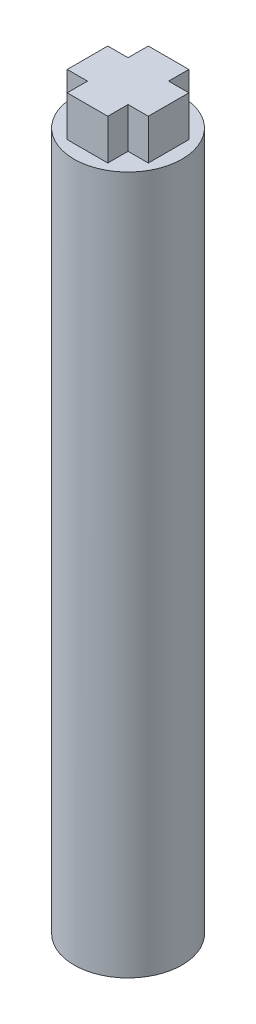
SolidWorks part; units mm, degrees
ref_plane "前视基准面" through (0, 0, 0) normal (0, 0, 1) x (1, 0, 0)
ref_plane "上视基准面" through (0, 0, 0) normal (0, 1, 0) x (1, 0, 0)
ref_plane "右视基准面" through (0, 0, 0) normal (1, 0, 0) x (0, 0, -1)
sketch "草图1" plane through (0, 0, 0) normal (0, 1, 0) x (1, 0, 0)
  line L1 (2.6744, -1.6246) -> (2.7442, 1.5038)
  line L2 (2.7442, 1.5038) -> (0.0698, 3.1285)
  line L3 (0.0698, 3.1285) -> (-2.6744, 1.6246)
  line L4 (-2.6744, 1.6246) -> (-2.7442, -1.5038)
  line L5 (-2.7442, -1.5038) -> (-0.0698, -3.1285)
  line L6 (-0.0698, -3.1285) -> (2.6744, -1.6246)
  circle A0 centre (0, 0) radius 4
  circle A1 centre (0, 0) radius 2.71 construction
  dimension "D1" = 8
  dimension "D2" = 2.71
extrude "凸台-拉伸1" add sketch "草图1" along normal blind 4.65
sketch "草图2" plane through (0, 4.65, 0) normal (0, 1, 0) x (1, 0, 0)
  circle A0 centre (0, 0) radius 4
extrude "凸台-拉伸2" add sketch "草图2" along normal blind 45
sketch "草图3" plane through (0, 4.65, 0) normal (0, -1, 0) x (1, 0, 0)
  circle A0 centre (0, 0) radius 2
  dimension "D1" = 4
extrude "切除-拉伸1" cut sketch "草图3" against normal blind 45
sketch "草图4" plane through (0, 49.65, 0) normal (0, 1, 0) x (1, 0, 0)
  circle A0 centre (0, 0) radius 4
extrude "凸台-拉伸3" add sketch "草图4" along normal blind 2
sketch "草图5" plane through (0, 51.65, 0) normal (0, 1, 0) x (1, 0, 0)
  line L0 (-1.5, 3) -> (-1.5, -3)
  line L1 (-1.5, 3) -> (1.5, 3)
  line L2 (-1.5, -3) -> (1.5, -3)
  line L3 (1.5, 3) -> (1.5, -3)
  circle A0 centre (0, 0) radius 4 construction
  dimension "D1" = 6
  dimension "D2" = 3
  dimension "D3" = 3
  dimension "D4" = 1.5
extrude "凸台-拉伸4" add sketch "草图5" along normal blind 3
sketch "草图6" plane through (0, 51.65, 0) normal (0, 1, 0) x (1, 0, 0)
  line L0 (-3, -1.5) -> (3, -1.5)
  line L1 (-3, -1.5) -> (-3, 1.5)
  line L2 (3, -1.5) -> (3, 1.5)
  line L3 (-3, 1.5) -> (3, 1.5)
  line L4 (-1.5, 3) -> (-1.5, -3) construction
  line L5 (1.5, -3) -> (1.5, 3) construction
  line L6 (1.5, 3) -> (-1.5, 3) construction
  line L7 (-1.5, -3) -> (1.5, -3) construction
  dimension "D1" = 1.5
  dimension "D2" = 1.5
  dimension "D3" = 1.5
  dimension "D4" = 1.5
extrude "凸台-拉伸5" add sketch "草图6" along normal blind 3
sketch "草图7" plane through (0, 0, 0) normal (0, -1, 0) x (1, 0, 0)
  circle A0 centre (0, 0) radius 6.0234
extrude "凸台-拉伸6" add sketch "草图7" along normal blind 1
sketch "草图8" plane through (0, -1, 0) normal (0, -1, 0) x (1, 0, 0)
  circle A0 centre (0, 0) radius 4
  dimension "D1" = 8
extrude "切除-拉伸2" cut sketch "草图8" against normal blind 0.5
sketch "草图10" plane through (0, -1, 0) normal (0, -1, 0) x (1, 0, 0)
  circle A0 centre (0, 0) radius 6.0234
extrude "切除-拉伸7" cut sketch "草图10" against normal blind 1
